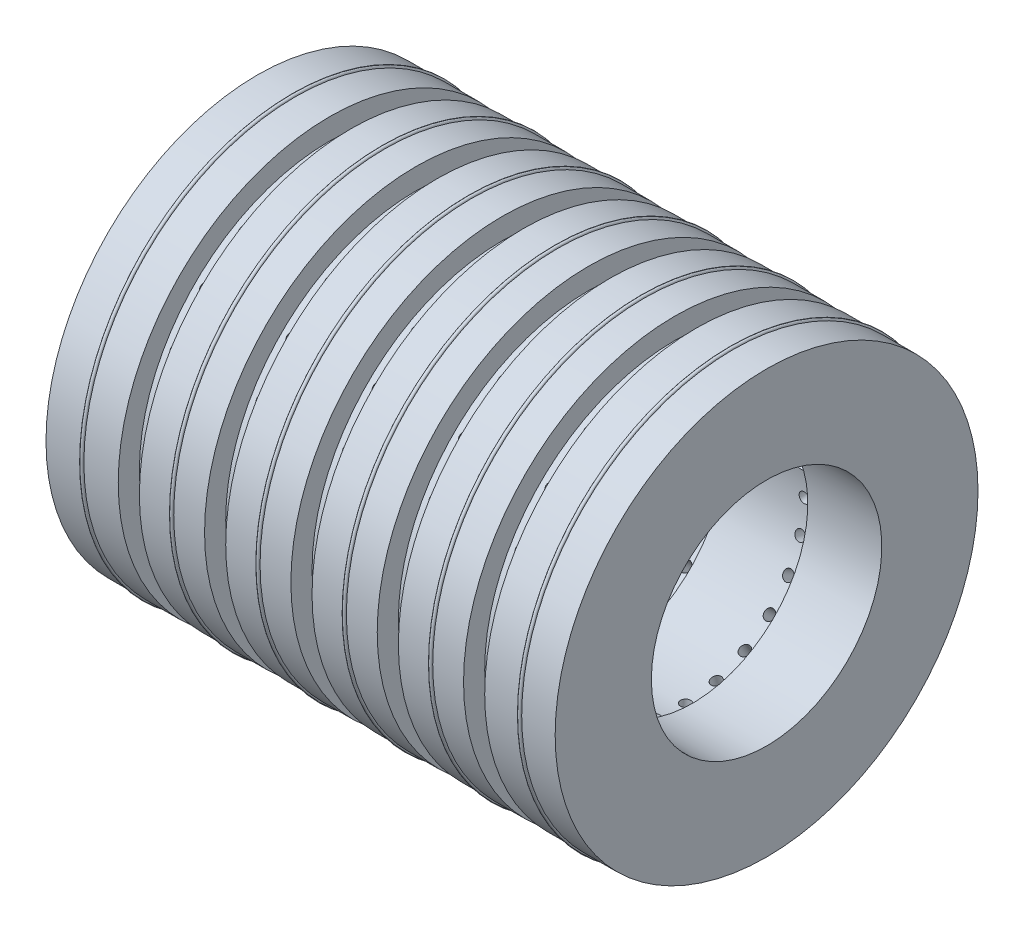
SolidWorks part; units mm, degrees
ref_plane "Front Plane" through (0, 0, 0) normal (0, 0, 1) x (1, 0, 0)
ref_plane "Top Plane" through (0, 0, 0) normal (0, 1, 0) x (1, 0, 0)
ref_plane "Right Plane" through (0, 0, 0) normal (1, 0, 0) x (0, 0, -1)
sketch "Sketch1" plane through (0, 0, 0) normal (0, 0, 1) x (1, 0, 0)
  line L0 (0, 0) -> (36.5459, 0) construction
  line L1 (-6.477, 9.5758) -> (-6.477, 15.24)
  line L3 (30.226, 15.24) -> (30.226, 8.3058)
  line L4 (30.226, 8.3058) -> (24.892, 8.3058)
  line L5 (24.892, 8.3058) -> (24.892, 8.5598)
  line L6 (24.892, 8.5598) -> (18.669, 8.5598)
  line L7 (18.669, 8.5598) -> (18.669, 8.8138)
  line L8 (18.669, 8.8138) -> (12.446, 8.8138)
  line L9 (12.446, 8.8138) -> (12.446, 9.0678)
  line L10 (12.446, 9.0678) -> (6.223, 9.0678)
  line L11 (6.223, 9.0678) -> (6.223, 9.3218)
  line L12 (6.223, 9.3218) -> (0, 9.3218)
  line L13 (0, 9.3218) -> (0, 9.5758)
  line L14 (0, 9.5758) -> (-6.477, 9.5758)
  line L15 (-6.477, 15.24) -> (-4.0005, 15.24)
  line L16 (-1.27, 15.24) -> (-1.27, 13.716)
  line L17 (-1.27, 13.716) -> (0.254, 13.716)
  line L18 (0.254, 13.716) -> (0.254, 15.24)
  line L19 (0.254, 15.24) -> (2.4765, 15.24)
  line L20 (4.953, 15.24) -> (4.953, 13.716)
  line L21 (4.953, 13.716) -> (6.477, 13.716)
  line L22 (6.477, 13.716) -> (6.477, 15.24)
  line L23 (6.477, 15.24) -> (8.6995, 15.24)
  line L24 (11.176, 15.24) -> (11.176, 13.716)
  line L25 (11.176, 13.716) -> (12.7, 13.716)
  line L26 (12.7, 13.716) -> (12.7, 15.24)
  line L27 (12.7, 15.24) -> (14.9225, 15.24)
  line L28 (17.399, 15.24) -> (17.399, 13.716)
  line L29 (17.399, 13.716) -> (18.923, 13.716)
  line L30 (18.923, 13.716) -> (18.923, 15.24)
  line L31 (18.923, 15.24) -> (21.1455, 15.24)
  line L32 (23.622, 15.24) -> (23.622, 13.716)
  line L33 (23.622, 13.716) -> (25.146, 13.716)
  line L34 (25.146, 13.716) -> (25.146, 15.24)
  line L35 (25.146, 15.24) -> (27.559, 15.24)
  line L36 (-3.7465, 15.24) -> (-1.27, 15.24)
  line L37 (2.7305, 15.24) -> (4.953, 15.24)
  line L38 (8.9535, 15.24) -> (11.176, 15.24)
  line L39 (15.1765, 15.24) -> (17.399, 15.24)
  line L40 (21.3995, 15.24) -> (23.622, 15.24)
  line L41 (27.813, 15.24) -> (30.226, 15.24)
  line L42 (-4.0005, 15.24) -> (-3.7465, 15.24) construction
  line L43 (2.4765, 15.24) -> (2.7305, 15.24) construction
  line L44 (8.6995, 15.24) -> (8.9535, 15.24) construction
  line L45 (14.9225, 15.24) -> (15.1765, 15.24) construction
  line L46 (21.1455, 15.24) -> (21.3995, 15.24) construction
  line L47 (27.559, 15.24) -> (27.813, 15.24) construction
  arc A9 (21.3995, 15.24) -> (21.1455, 15.24) centre (21.2725, 15.24) ccw
  arc A10 (15.1765, 15.24) -> (14.9225, 15.24) centre (15.0495, 15.24) ccw
  arc A11 (8.9535, 15.24) -> (8.6995, 15.24) centre (8.8265, 15.24) ccw
  arc A12 (2.7305, 15.24) -> (2.4765, 15.24) centre (2.6035, 15.24) ccw
  arc A13 (-3.7465, 15.24) -> (-4.0005, 15.24) centre (-3.8735, 15.24) ccw
  arc A14 (27.813, 15.24) -> (27.559, 15.24) centre (27.686, 15.24) ccw
  point P37 (-6.477, 12.4079)
  dimension "D13" = 0.254
  dimension "D2" = 0.254
  dimension "D4" = 15.24
  dimension "D5" = 1.524
  dimension "D6" = 1.524
  dimension "D8" = 1.524
  dimension "D9" = 1.524
  dimension "D10" = 1.524
  dimension "D11" = 1.524
  dimension "D3" = 6.223
  dimension "D12" = 36.703
  dimension "D14" = 9.5758
  dimension "D7" = 0.254
  dimension "D15" = 0.254
  dimension "D16" = 0.254
  dimension "D17" = 0.254
  dimension "D18" = 0.254
  dimension "D19" = 5.334
  dimension "D20" = 6.477
revolve "Revolve1" add sketch "Sketch1" angle 360 about L0
ref_plane "Plane1" through (-0.508, 0, 0) normal (-1, 0, 0) x (0, 0, 1)
ref_plane "Plane2" through (5.715, 0, 0) normal (-1, 0, 0) x (0, 0, 1)
ref_plane "Plane3" through (11.938, 0, 0) normal (1, 0, 0) x (0, 0, -1)
ref_plane "Plane4" through (18.161, 0, 0) normal (-1, 0, 0) x (0, 0, 1)
ref_plane "Plane5" through (24.384, 0, 0) normal (1, 0, 0) x (0, 0, -1)
ref_plane "Plane6" through (0, 15.24, 0) normal (0, 1, 0) x (1, 0, 0)
ref_axis "Axis1" through (0, 0, 0) along (-1, 0, 0)
sketch "Sketch4" plane through (-0.508, 0, 0) normal (-1, 0, 0) x (0, 0, 1)
  point P0 (0, 0)
sketch "Sketch5" plane through (5.715, 0, 0) normal (-1, 0, 0) x (0, 0, 1)
  point P0 (0, 0)
sketch "Sketch6" plane through (11.938, 0, 0) normal (1, 0, 0) x (0, 0, -1)
  point P0 (0, 0)
sketch "Sketch7" plane through (18.161, 0, 0) normal (-1, 0, 0) x (0, 0, 1)
  point P0 (0, 0)
sketch "Sketch8" plane through (24.384, 0, 0) normal (1, 0, 0) x (0, 0, -1)
  point P0 (0, 0)
sketch "Sketch9" plane through (0, 15.24, 0) normal (0, 1, 0) x (1, 0, 0)
  point P0 (24.384, 0)
  point P2 (18.161, 0)
  point P4 (11.938, 0)
  point P6 (5.715, 0)
  point P11 (-0.508, 0)
hole_wizard "#69 (0.0292) Diameter Hole1" positions "Sketch9" profile "Sketch10" hole size "#69" standard "ANSI Inch" end condition up to next
sketch "Sketch10" plane through (24.384, 15.24, 0) normal (1, 0, 0) x (0, 0, 1)
  line L0 (0, 0) -> (0, 6.6802)
  line L1 (0, 6.6802) -> (0.3708, 6.6802)
  line L2 (0.3708, 6.6802) -> (0.3708, 0)
  line L5 (0.3708, 0) -> (0, 0)
  line L11 (0, -6.35) -> (0, 107.95) construction
  dimension "Thru Hole Dia." = 0.7417
  dimension "Thru Hole Depth" = 6.6802
pattern_circular "CirPattern1" count 24 every 15 about axis through (0, 0, 0) along (-1, 0, 0) of "#69 (0.0292) Diameter Hole1"
equation "\"kero_radius\"=0.23622in"
equation "\"lox_radius\"=0.23622in"
equation "\"Cavity_width\"=0.031in"
equation "\"tooth_width\"=0.01in"
equation "\"cavity_depth\"=0.031in"
equation "\"seal_step\"=0.01in"
equation "\"purge_length\"=0.04in"
equation "\"D2@Sketch1\"=\"seal_step\""
equation "\"insert_radius\" = 0.6in"
equation "\"recycle_groove width\" = 0.06in"
equation "\"D5@Sketch1\"=\"recycle_groove width\""
equation "\"recycle_groove_depth\" = 0.06in"
equation "\"D6@Sketch1\"=\"recycle_groove_depth\""
equation "\"N2_purge_width\"= .06in"
equation "\"N2_purge_depth\"= .06in"
equation "\"drain_width\"= .06in"
equation "\"drain_depth\"= .06in"
equation "\"D9@Sketch1\"=\"drain_depth\""
equation "\"D8@Sketch1\"=\"drain_width\""
equation "\"D10@Sketch1\"=\"N2_purge_depth\""
equation "\"D11@Sketch1\"=\"N2_purge_width\""
equation "\"radial_clearance\"= .002in"
equation "\"D3@Sketch1\"=\"tooth_width\"*5+\"Cavity_width\"*5+\"purge_length\""
equation "\"Insert_Length\"= \"D12@Sketch1\""
equation "\"InsertLength\"= 1.445in"
equation "\"D4@Sketch1\"=\"insert_radius\""
equation "\"bumb_radius\"= 0.01"
equation "\"D13@Sketch1\"=\"bumb_radius\""
equation "\"bearing_radius\"= 0.629921"
equation "\"bearing_width\"=0.393701"
equation "\"IPS_flange_width\"= .2in"
equation "\"IPS_flange_radius\" = 2.2in"
equation "\"IPS_LOX_male_radius\"= .9in"
equation "\"IPS_Kero_male_radius\" = .9in"
equation "\"IPS_radius\"= 1.4in"
equation "\"lox_in_radius\"=.375in"
equation "\"D14@Sketch1\"=\"lox_in_radius\"+\"radial_clearance\""
equation "\"D7@Sketch1\"=(\"drain_width\"-\"purge_length\")/2"
equation "\"D15@Sketch1\"=(\"drain_width\"-\"purge_length\")/2"
equation "\"D16@Sketch1\"=(\"drain_width\"-\"purge_length\")/2"
equation "\"D17@Sketch1\"=(\"drain_width\"-\"purge_length\")/2"
equation "\"D18@Sketch1\"=(\"drain_width\"-\"purge_length\")/2"
